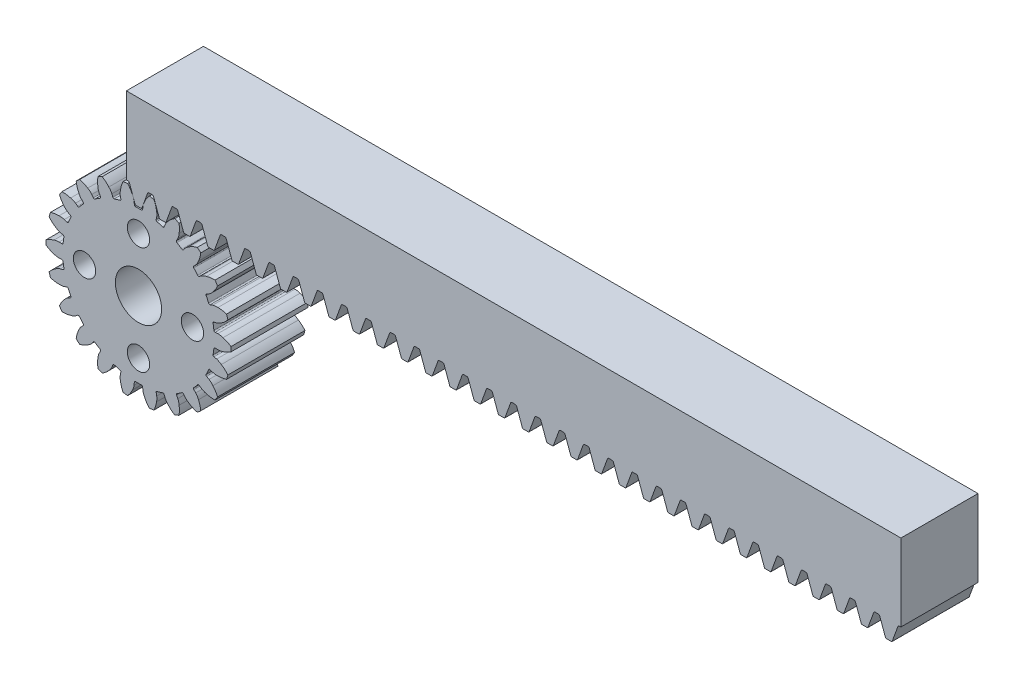
SolidWorks part; units mm, degrees
material "PVC 0.007 Plasticizado"
ref_plane "Plano frontal" through (0, 0, 0) normal (0, 0, 1) x (1, 0, 0)
ref_plane "Plano superior" through (0, 0, 0) normal (0, 1, 0) x (1, 0, 0)
ref_plane "Plano direito" through (0, 0, 0) normal (1, 0, 0) x (0, 0, -1)
sketch "Esboço1" plane through (0, 0, 0) normal (0, 0, 1) x (1, 0, 0)
  circle A108 centre (0, 0) radius 12
  dimension "D1" = 24
extrude "Ressalto-extrusão1" add sketch "Esboço1" along normal mid plane 10
sketch "Esboço2" plane through (0, 0, 5) normal (0, 0, 1) x (1, 0, 0)
  line L0 (0, 0) -> (0, 9.833) construction
  line L1 (0, 0) -> (0.7846, 10.972) construction
  line L2 (0, 0) -> (-0.7846, 10.972) construction
  line L3 (-0.7846, 10.972) -> (0.7846, 10.972) construction
  line L4 (0.5674, 10.3211) -> (0.5426, 9.9742)
  line L5 (-0.5674, 10.3211) -> (-0.5426, 9.9742)
  line L6 (0, 0) -> (-1.4097, 11.9169) construction
  circle A0 centre (0, 0) radius 11 construction
  circle A1 centre (0, 0) radius 10.3367 construction
  arc A2 (0.3769, 9.8258) -> (-0.3769, 9.8258) centre (0, 0) ccw
  circle A3 centre (0, 0) radius 12 construction
  arc A4 (1.4097, 11.9169) -> (-1.4097, 11.9169) centre (0, 0) ccw
  arc A5 (0.7846, 10.972) -> (1.4097, 11.9169) centre (3.9692, 9.5443) cw
  arc A6 (0.7846, 10.972) -> (0.5674, 10.3211) centre (2.6028, 10.0036) ccw
  arc A7 (-0.7846, 10.972) -> (-0.5674, 10.3211) centre (-2.6028, 10.0036) cw
  arc A8 (-0.7846, 10.972) -> (-1.4097, 11.9169) centre (-3.9692, 9.5443) ccw
  arc A9 (0.5426, 9.9742) -> (0.3769, 9.8258) centre (0.383, 9.9857) cw
  arc A10 (-0.5426, 9.9742) -> (-0.3769, 9.8258) centre (-0.383, 9.9857) ccw
  point P19 (0.5315, 9.8186)
  point P22 (-0.5315, 9.8186)
  dimension "D1" = 22
  dimension "D2" = 20.6734
  dimension "D3" = 19.666
  dimension "D7" = 3.49
  dimension "D8" = 2.06
  dimension "D10" = 6.747
  dimension "D4" = 0.16
  dimension "D5" = 4.09
  dimension "D6" = 1.5691
  dimension "D9" = 4.09
extrude "Corte-extrusão1" cut sketch "Esboço2" against normal through all
pattern_circular "PadrãoCircular2" count 22 over 360 about axis through (0, 0, 5) along (0, 0, 1) of "Corte-extrusão1"
sketch "Esboço3" plane through (0, 0, 5) normal (0, 0, 1) x (1, 0, 0)
  line L0 (-7, 0) -> (7, 0) construction
  line L1 (0, 7) -> (0, -7) construction
  circle A0 centre (0, 0) radius 3
  circle A1 centre (0, 7) radius 1.45
  circle A2 centre (0, -7) radius 1.45
  circle A3 centre (-7, 0) radius 1.45
  circle A4 centre (7, 0) radius 1.45
  point P6 (0, 0)
  point P9 (0, 0)
  dimension "D1" = 6
  dimension "D4" = 2.9
  dimension "D5" = 2.9
  dimension "D2" = 14
  dimension "D3" = 14
extrude "Corte-extrusão3" cut sketch "Esboço3" against normal through all
sketch "Esboço4" plane through (0, 0, 0) normal (0, 0, 1) x (1, 0, 0)
  line L0 (0, 10) -> (0, 12.25) construction
  line L17 (1.2282, 12.25) -> (-1.2282, 12.25) construction
  line L18 (1.1803, 12.1184) -> (0.4332, 10.0658)
  line L19 (0.3392, 10) -> (-0.3392, 10)
  line L20 (-1.1803, 12.1184) -> (-0.4332, 10.0658)
  line L21 (0, 9.833) -> (0, 12.7293) construction
  line L22 (-0.7732, 11) -> (0.7732, 11) construction
  line L23 (-1.3682, 12.25) -> (-1.5708, 12.25)
  line L24 (-1.5708, 12.25) -> (-1.5708, 22.25)
  line L25 (-1.5708, 22.25) -> (1.5708, 22.25)
  line L26 (1.5708, 22.25) -> (1.5708, 12.25)
  line L27 (1.5708, 12.25) -> (1.3682, 12.25)
  circle A0 centre (0, 0) radius 11 construction
  arc A1 (-0.7846, 10.972) -> (-1.4097, 11.9169) centre (-3.9692, 9.5443) ccw construction
  arc A3 (-0.5674, 10.3211) -> (-0.7846, 10.972) centre (-2.6028, 10.0036) ccw construction
  arc A4 (-0.3392, 10) -> (-0.4332, 10.0658) centre (-0.3392, 10.1) cw
  arc A5 (0.4332, 10.0658) -> (0.3392, 10) centre (0.3392, 10.1) cw
  arc A6 (1.3682, 12.25) -> (1.1803, 12.1184) centre (1.3682, 12.05) ccw
  arc A7 (-1.3682, 12.25) -> (-1.1803, 12.1184) centre (-1.3682, 12.05) cw
  dimension "D7" = 0.1
  dimension "D8" = 0.2
  dimension "D1" = 1.25
  dimension "D2" = 1
  dimension "D3" = 20
  dimension "D4" = 3.5011
  dimension "D5" = 10
  dimension "D6" = 3.1416
extrude "Ressalto-extrusão2" add sketch "Esboço4" along normal mid plane 10 separate body
pattern_linear "Padrão linear6" count 32 spacing 3.14 along (1, 0, 0) of "Ressalto-extrusão2"
sketch "Esboço6" plane through (-1.5708, 0, 0) normal (-1, 0, 0) x (0, 0, 1)
  line L1 (-5, 22.25) -> (5, 22.25)
  line L2 (-5, 22.25) -> (-5, 12.25)
  line L3 (-5, 12.25) -> (5, 12.25)
  line L4 (5, 22.25) -> (5, 12.25)
extrude "Ressalto-extrusão4" add sketch "Esboço6" against normal blind 100
